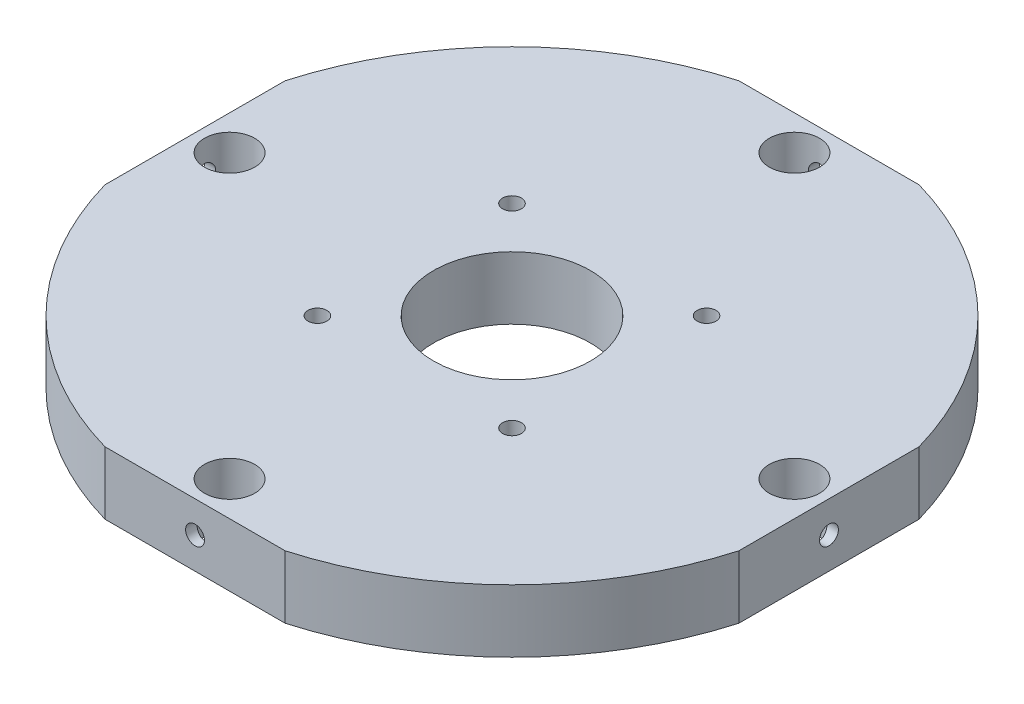
SolidWorks part; units mm, degrees
ref_plane "Front Plane" through (0, 0, 0) normal (0, 0, 1) x (1, 0, 0)
ref_plane "Top Plane" through (0, 0, 0) normal (0, 1, 0) x (1, 0, 0)
ref_plane "Right Plane" through (0, 0, 0) normal (1, 0, 0) x (0, 0, -1)
sketch "Sketch1" plane through (0, 0, 0) normal (0, 1, 0) x (1, 0, 0)
  circle A0 centre (0, 0) radius 52.5
  dimension "D1" = 105
extrude "Boss-Extrude1" add sketch "Sketch1" along normal blind 10
sketch "Sketch3" plane through (0, 10, 0) normal (0, 1, 0) x (1, 0, 0)
  line L0 (0, 45) -> (0, 0) construction
  line L1 (0, 0) -> (0, -45) construction
  circle A0 centre (0, 45) radius 4
  circle A1 centre (45, 0) radius 4
  circle A2 centre (0, -45) radius 4
  circle A3 centre (-45, 0) radius 4
  dimension "D2" = 8
  dimension "D1" = 45
  dimension "D3" = 4
extrude "Cut-Extrude1" cut sketch "Sketch3" against normal through all
sketch "Sketch4" plane through (0, 10, 0) normal (0, 1, 0) x (1, 0, 0)
  line L0 (-14.3527, -50.5) -> (14.3527, -50.5)
  line L1 (0, -52.5) -> (50000, -52.5) construction
  line L2 (50.5, -14.3527) -> (50.5, 14.3527)
  line L3 (14.3527, 50.5) -> (-14.3527, 50.5)
  line L4 (-50.5, 14.3527) -> (-50.5, -14.3527)
  circle A0 centre (0, 0) radius 52.5 construction
  dimension "D1" = 2
  dimension "D2" = 4
extrude "Cut-Extrude-Thin1" cut sketch "Sketch4" against normal through all thin thin type one direction wall 10
sketch "Sketch5" plane through (0, 0, 50.5) normal (0, 0, 1) x (1, 0, 0)
  line L0 (-14.3527, 0) -> (14.3527, 0) construction
  line L1 (0, 10) -> (0, 0) construction
  line L2 (-14.3527, 10) -> (14.3527, 10) construction
  circle A0 centre (0, 5) radius 1.5
  point P4 (0, 0)
  dimension "D1" = 3
extrude "Cut-Extrude3" cut sketch "Sketch5" against normal up to next
pattern_circular "CirPattern1" count 4 over 360 about axis through (0, 10, 0) along (0, -1, 0) of "Cut-Extrude3"
sketch "Sketch6" plane through (0, 10, 0) normal (0, 1, 0) x (1, 0, 0)
  circle A0 centre (0, 0) radius 12.5
  dimension "D1" = 25
extrude "Cut-Extrude4" cut sketch "Sketch6" against normal through all
sketch "Sketch7" plane through (0, 10, 0) normal (0, 1, 0) x (1, 0, 0)
  line L0 (0, 50.5) -> (0, -50.5) construction
  line L1 (14.3527, 50.5) -> (-14.3527, 50.5) construction
  line L2 (-14.3527, -50.5) -> (14.3527, -50.5) construction
  line L3 (-50.5, 0) -> (50.5, 0) construction
  line L4 (-50.5, 14.3527) -> (-50.5, -14.3527) construction
  line L5 (50.5, -14.3527) -> (50.5, 14.3527) construction
  circle A0 centre (-15.5, 15.5) radius 1.5
  circle A1 centre (15.5, 15.5) radius 1.5
  circle A2 centre (15.5, -15.5) radius 1.5
  circle A3 centre (-15.5, -15.5) radius 1.5
  dimension "D1" = 3
  dimension "D2" = 15.5
  dimension "D3" = 15.5
extrude "Cut-Extrude5" cut sketch "Sketch7" against normal through all
